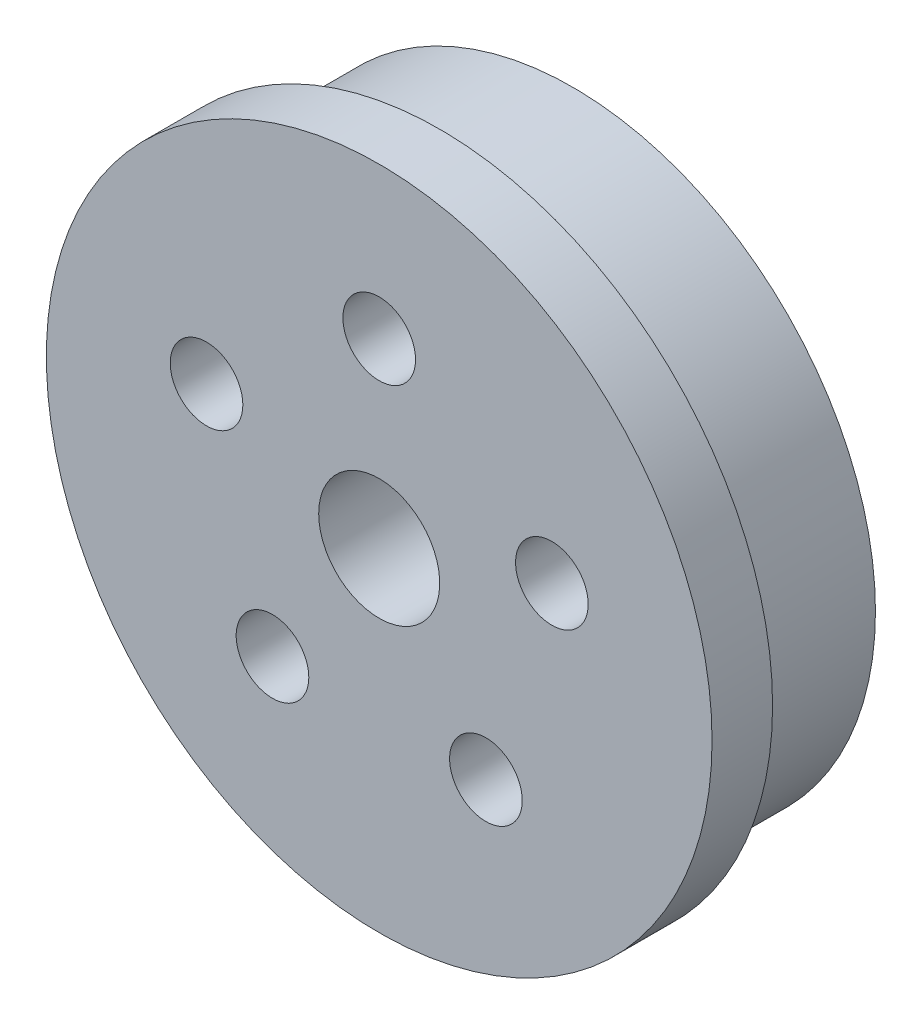
SolidWorks part; units mm, degrees
material "A2017"
ref_plane "正面" through (0, 0, 0) normal (0, 0, 1) x (1, 0, 0)
ref_plane "平面" through (0, 0, 0) normal (0, 1, 0) x (1, 0, 0)
ref_plane "右側面" through (0, 0, 0) normal (1, 0, 0) x (0, 0, -1)
sketch "ｽｹｯﾁ1" plane through (0, 0, 0) normal (0, 0, 1) x (1, 0, 0)
  circle A0 centre (0, 0) radius 12.5
  circle A1 centre (0, 7.5) radius 3
  circle A2 centre (0, 0) radius 7.5 construction
  circle A3 centre (7.1329, 2.3176) radius 3
  circle A4 centre (4.4084, -6.0676) radius 3
  circle A5 centre (-4.4084, -6.0676) radius 3
  circle A6 centre (-7.1329, 2.3176) radius 3
  point P16 (0, 0)
  dimension "D1" = 25
  dimension "D2" = 15
  dimension "D3" = 6
  dimension "D4" = 5
extrude "ﾎﾞｽ - 押し出し1" add sketch "ｽｹｯﾁ1" along normal blind 8
sketch "ｽｹｯﾁ2" plane through (0, 0, 8) normal (0, 0, 1) x (1, 0, 0)
  circle A0 centre (-7.1329, 2.3176) radius 3 construction
  circle A1 centre (0, 7.5) radius 3 construction
  circle A2 centre (7.1329, 2.3176) radius 3 construction
  circle A3 centre (4.4084, -6.0676) radius 3 construction
  circle A4 centre (-4.4084, -6.0676) radius 3 construction
  circle A5 centre (-7.1329, 2.3176) radius 3
  circle A6 centre (0, 7.5) radius 3
  circle A7 centre (7.1329, 2.3176) radius 3
  circle A8 centre (4.4084, -6.0676) radius 3
  circle A9 centre (-4.4084, -6.0676) radius 3
  circle A10 centre (0, 7.5) radius 1.5
  circle A11 centre (7.1329, 2.3176) radius 1.5
  circle A12 centre (4.4084, -6.0676) radius 1.5
  circle A13 centre (-4.4084, -6.0676) radius 1.5
  circle A14 centre (-7.1329, 2.3176) radius 1.5
  point P26 (0, 0)
  dimension "D1" = 3
  dimension "D2" = 5
extrude "ﾎﾞｽ - 押し出し2" add sketch "ｽｹｯﾁ2" against normal blind 4.5
sketch "ｽｹｯﾁ3" plane through (0, 0, 8) normal (0, 0, 1) x (1, 0, 0)
  circle A0 centre (0, 0) radius 13.75
  circle A2 centre (0, 0) radius 12.5
  circle A3 centre (0, 0) radius 12.5
  dimension "D1" = 0
  dimension "D2" = 27.5
extrude "ﾎﾞｽ - 押し出し3" add sketch "ｽｹｯﾁ3" against normal blind 2.5
sketch "ｽｹｯﾁ4" plane through (0, 0, 0) normal (0, 0, -1) x (-1, 0, 0)
  circle A0 centre (0, 0) radius 2.5
  dimension "D1" = 5
extrude "ｶｯﾄ - 押し出し1" cut sketch "ｽｹｯﾁ4" against normal through all
